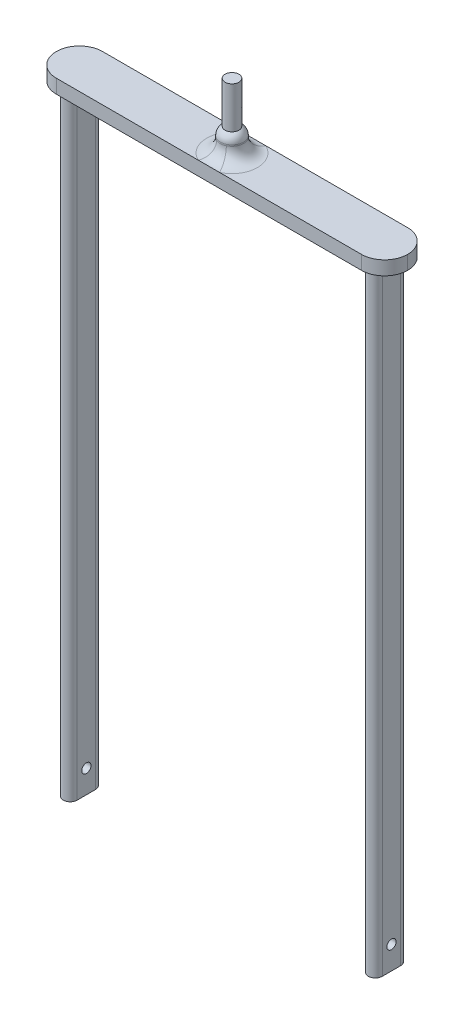
SolidWorks part; units mm, degrees
ref_plane "Alzado" through (0, 0, 0) normal (0, 0, 1) x (1, 0, 0)
ref_plane "Planta" through (0, 0, 0) normal (0, 1, 0) x (1, 0, 0)
ref_plane "Vista lateral" through (0, 0, 0) normal (1, 0, 0) x (0, 0, -1)
sketch "Croquis1" plane through (0, 0, 0) normal (0, 1, 0) x (1, 0, 0)
  line L0 (0, 0) -> (0, 11.6968) construction
  line L1 (0, 0) -> (13.9819, 0) construction
  line L2 (-38, 0) -> (-38, 5)
  line L3 (-38, 5) -> (0, 5)
  line L4 (0, 5) -> (38, 5)
  line L5 (38, 5) -> (38, 0)
  line L6 (38, 0) -> (38, -5)
  line L7 (38, -5) -> (0, -5)
  line L8 (0, -5) -> (-38, -5)
  line L9 (-38, -5) -> (-38, 0)
  dimension "D1" = 5
  dimension "D2" = 5
  dimension "D3" = 38
  dimension "D4" = 38
extrude "Saliente-Extruir1" add sketch "Croquis1" along normal blind 3
sketch "Croquis2" plane through (0, 3, 0) normal (0, 1, 0) x (1, 0, 0)
  circle A0 centre (0, 0) radius 2.5
extrude "Saliente-Extruir2" add sketch "Croquis2" along normal blind 5
sketch "Croquis3" plane through (0, 8, 0) normal (0, 1, 0) x (1, 0, 0)
  circle A0 centre (0, 0) radius 1.5
extrude "Saliente-Extruir3" add sketch "Croquis3" along normal blind 9
fillet "Redondeo1" radius 2 1 edges at (0, 8, 2.5)
fillet "Redondeo2" radius 3 1 edges at (0, 3, -2.5)
fillet "Redondeo3" radius 5 4 edges at (38, 1.5, 5) (38, 1.5, -5) (-38, 1.5, -5) (-38, 1.5, 5)
sketch "Croquis4" plane through (0, 0, 0) normal (0, -1, 0) x (1, 0, 0)
  line L0 (-33, 9.9485) -> (-33, -11.9485) construction
  line L1 (39, 0) -> (-31.5, 0) construction
  line L2 (-32.5, 0) -> (-39, 0) construction
  line L6 (-31.5, 2) -> (-31.5, 0)
  line L7 (-31.5, 0) -> (-31.5, -2)
  line L11 (0, 0) -> (0, -18.8608) construction
  line L14 (31.5, 0) -> (31.5, -2)
  line L15 (31.5, 2) -> (31.5, 0)
  line L22 (-34.5, 2) -> (-34.5, -2)
  line L23 (34.5, 2) -> (34.5, -2)
  arc A0 (-31.5, 2) -> (-34.5, 2) centre (-33, 2) ccw
  arc A1 (-34.5, -2) -> (-31.5, -2) centre (-33, -2) ccw
  arc A2 (34.5, -2) -> (31.5, -2) centre (33, -2) cw
  arc A3 (31.5, 2) -> (34.5, 2) centre (33, 2) cw
  point P24 (-33, 3.5)
  point P25 (-33, -3.5)
  dimension "D2" = 2
  dimension "D1" = 33
  dimension "D3" = 2
  dimension "D4" = 7
extrude "Saliente-Extruir6" add sketch "Croquis4" along normal blind 133
sketch "Croquis7" plane through (-34.5, 0, 0) normal (-1, 0, 0) x (0, 0, 1)
  line L0 (2, -133) -> (-2, -133) construction
  circle A0 centre (0, -128) radius 1
  dimension "D1" = 5
extrude "Cortar-Extruir6" cut sketch "Croquis7" against normal blind 140
